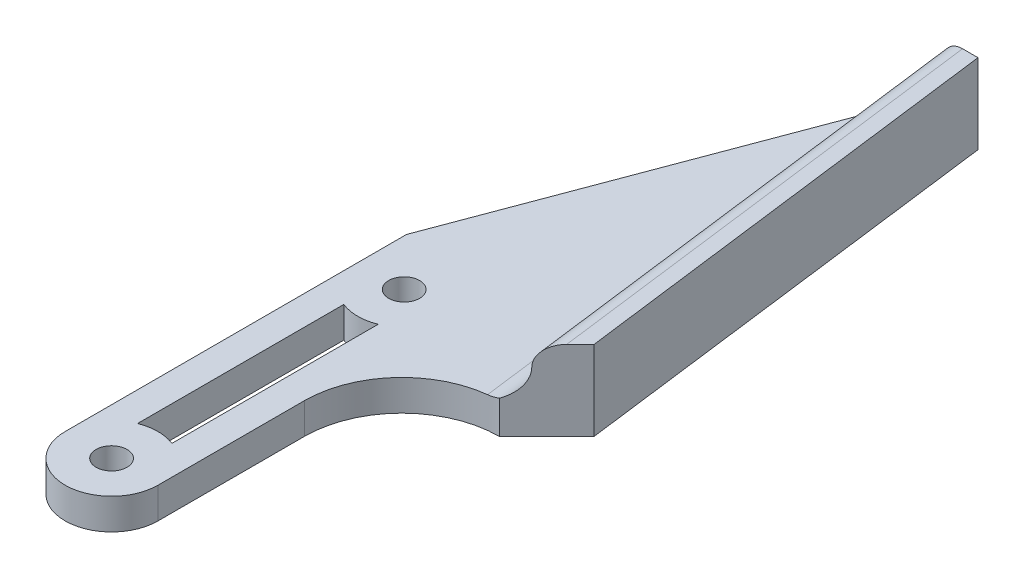
SolidWorks part; units mm, degrees
ref_plane "Alzado" through (0, 0, 0) normal (0, 0, 1) x (1, 0, 0)
ref_plane "Planta" through (0, 0, 0) normal (0, 1, 0) x (1, 0, 0)
ref_plane "Vista lateral" through (0, 0, 0) normal (1, 0, 0) x (0, 0, -1)
sketch "Croquis1" plane through (0, 0, 0) normal (0, 1, 0) x (1, 0, 0)
  line L0 (-12.5, 40) -> (12.5, -40) construction
  line L1 (-12.5, 40) -> (12.5, 40) construction
  line L2 (-12.5, 40) -> (-12.5, -40) construction
  line L3 (-12.5, -40) -> (12.5, -40) construction
  line L4 (12.5, 40) -> (12.5, -40) construction
  line L5 (-12.5, 0) -> (-12.5, -40)
  line L6 (-12.5, -40) -> (-2.975, -40)
  line L7 (-2.975, -40) -> (-2.975, -20)
  line L8 (7.025, -10) -> (12.5, -10)
  line L9 (12.5, -10) -> (12.5, 40)
  line L10 (12.5, 40) -> (2.5, 40)
  line L11 (2.5, 40) -> (-12.5, 0)
  circle A0 centre (-7.7375, -5) radius 1.5875
  circle A1 centre (-7.7375, -35) radius 1.5875
  arc A2 (-2.975, -20) -> (7.025, -10) centre (7.025, -20) cw
  dimension "D5" = 3.175
  dimension "D6" = 3.175
  dimension "D12" = 10
  dimension "D1" = 25
  dimension "D2" = 80
  dimension "D3" = 9.525
  dimension "D4" = 30
  dimension "D7" = 4.7625
  dimension "D8" = 5
  dimension "D9" = 10
  dimension "D10" = 40
  dimension "D11" = 50
extrude "Saliente-Extruir1" add sketch "Croquis1" along normal blind 3.175
sketch "Croquis2" plane through (0, 3.175, 0) normal (0, 1, 0) x (1, 0, 0)
  line L0 (12.5, -10) -> (6.1, 40)
  line L1 (12.5, 40) -> (2.5, 40) construction
  line L2 (6.1, 40) -> (12.5, 40)
  line L3 (12.5, 40) -> (12.5, -10)
  dimension "D1" = 6.4
extrude "Cortar-Extruir1" cut sketch "Croquis2" against normal blind 3.175
sketch "Croquis3" plane through (0, 3.175, 0) normal (0, 1, 0) x (1, 0, 0)
  line L1 (-2.975, -40) -> (-2.975, -20) construction
  line L2 (-12.5, -35) -> (-12.5, -40)
  line L3 (-12.5, -40) -> (-2.975, -40)
  line L4 (-2.975, -40) -> (-2.975, -35)
  line L5 (-9.5, -9.4271) -> (-9.5, -30.5756)
  line L6 (-5.975, -14.8038) -> (-5.975, -30.5756)
  line L7 (-12.5, 0) -> (-12.5, -40) construction
  line L8 (-5.975, -14.8038) -> (-5.975, -9.4271)
  line L22 (7.025, -6) -> (7.9554, -6)
  line L23 (7.9554, -6) -> (3.2646, 30.6468)
  line L24 (3.2646, 30.6468) -> (-8.5, -0.7253)
  line L25 (-8.5, -0.7253) -> (-8.5, -36)
  line L26 (-8.5, -36) -> (-6.975, -36)
  line L27 (-6.975, -36) -> (-6.975, -20)
  line L28 (7.025, -6) -> (7.9554, -6)
  arc A2 (-9.5, -9.4271) -> (-5.975, -9.4271) centre (-7.7375, -5) ccw
  arc A3 (-12.5, -35) -> (-2.975, -35) centre (-7.7375, -35) ccw
  arc A4 (-5.975, -30.5756) -> (-9.5, -30.5756) centre (-7.7375, -35) ccw
  arc A6 (7.025, -6) -> (-6.975, -20) centre (7.025, -20) ccw
  dimension "D1" = 9.53
  dimension "D2" = 3
  dimension "D3" = 3
  dimension "D5" = 4
extrude "Cortar-Extruir3" cut sketch "Croquis3" against normal blind 10 contours A4 L6 L8 A2 L5 | A3 L4 L3 L2 region at (-9.0022, 3.175, 20.0013) region at (-7.5171, 3.175, 18.7603) region at (-6.4486, 3.175, 23.4107)
sketch "Croquis5" plane through (0, 3.175, 0) normal (0, 1, 0) x (1, 0, 0)
  line L0 (6.1, 40) -> (12.5, -10) construction
  line L1 (7.025, -10) -> (11.8787, -5.1463)
  line L2 (11.8787, -5.1463) -> (12.5, -10)
  line L3 (12.5, -10) -> (7.025, -10)
  dimension "D3" = 45
extrude "Cortar-Extruir8" cut sketch "Croquis5" against normal blind 10
sketch "Esquisse1" plane through (0, 3.175, 0) normal (0, 1, 0) x (1, 0, 0)
  line L0 (11.8787, -5.1463) -> (6.1, 40)
  line L1 (6.1, 40) -> (2.5, 40)
  line L2 (2.5, 40) -> (8.6872, -8.3378)
  line L3 (11.8787, -5.1463) -> (7.025, -10) construction
  line L4 (8.6872, -8.3378) -> (11.8787, -5.1463)
extrude "Boss.-Extru.1" add sketch "Esquisse1" along normal blind 5
fillet "Congé1" radius 2 1 edges at (5.5936, 8.175, -15.8311)
fillet "Congé2" radius 3 1 edges at (5.5936, 3.175, -15.8311)
